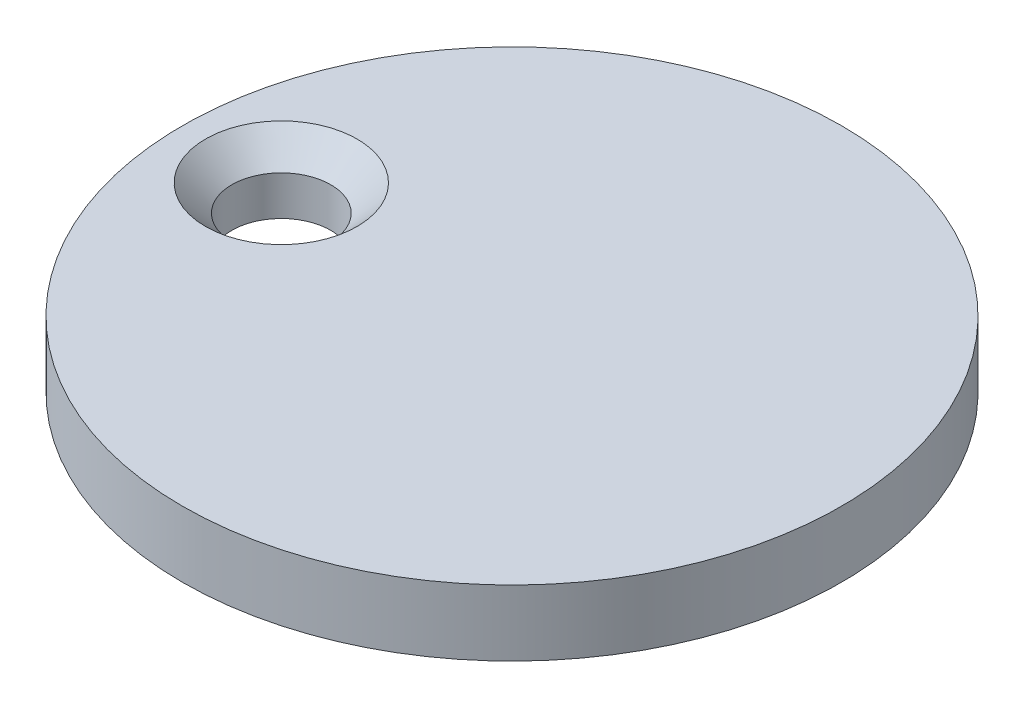
SolidWorks part; units mm, degrees
ref_plane "Front" through (0, 0, 0) normal (0, 0, 1) x (1, 0, 0)
ref_plane "Top" through (0, 0, 0) normal (0, 1, 0) x (1, 0, 0)
ref_plane "Right" through (0, 0, 0) normal (1, 0, 0) x (0, 0, -1)
sketch "Sketch1" plane through (0, 0, 0) normal (0, 1, 0) x (1, 0, 0)
  circle A0 centre (0, 0) radius 50
  circle A1 centre (-35, 0) radius 7.5
  point P5 (0, 0)
  dimension "D1" = 100
  dimension "D2" = 15
  dimension "D3" = 35
extrude "Boss-Extrude1" add sketch "Sketch1" along normal blind 10
chamfer "Chamfer1" distance 4 angle 45 1 edges at (-35, 10, 7.5)
